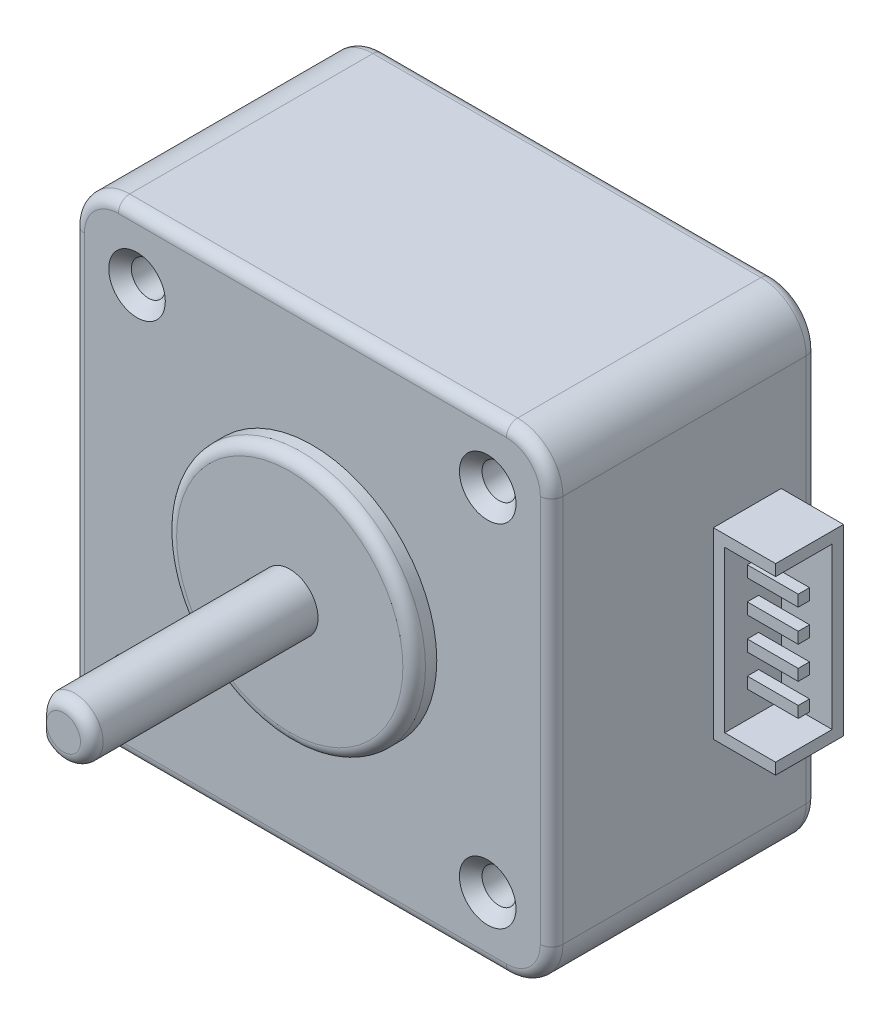
SolidWorks part; units mm, degrees
ref_plane "Top Plane" through (0, 0, 0) normal (0, 0, 1) x (1, 0, 0)
ref_plane "Right Plane" through (0, 0, 0) normal (0, 1, 0) x (1, 0, 0)
ref_plane "Front Plane" through (0, 0, 0) normal (1, 0, 0) x (0, 0, -1)
sketch "Sketch1" plane through (0, 0, 0) normal (0, 0, 1) x (1, 0, 0)
  line L0 (-21.15, 21.15) -> (21.15, -21.15) construction
  line L1 (-21.15, 21.15) -> (21.15, 21.15)
  line L2 (-21.15, 21.15) -> (-21.15, -21.15)
  line L3 (-21.15, -21.15) -> (21.15, -21.15)
  line L4 (21.15, 21.15) -> (21.15, -21.15)
  point P4 (0, 0)
  dimension "D1" = 42.3
extrude "Boss-Extrude1" add sketch "Sketch1" along normal blind 23.5
fillet "Fillet1" radius 4 4 edges at (-21.15, 21.15, 11.75) (21.15, 21.15, 11.75) (21.15, -21.15, 11.75) (-21.15, -21.15, 11.75)
sketch "Sketch2" plane through (0, 0, 23.5) normal (0, 0, 1) x (1, 0, 0)
  line L0 (-15.5, -15.5) -> (0, 0) construction
  line L1 (-15.5, -15.5) -> (-15.5, 0) construction
  line L2 (-15.5, 0) -> (0, 0) construction
  circle A0 centre (-15.5, -15.5) radius 1.5
  dimension "D1" = 3
  dimension "D2" = 15.5
extrude "Cut-Extrude1" cut sketch "Sketch2" against normal blind 5
chamfer "Chamfer1" distance 1 angle 45 1 edges at (-14, -15.5, 23.5)
ref_axis "Axis1" through (0, 0, 23.5) along (0, 0, 1)
pattern_circular "CirPattern1" count 4 over 360 about axis through (0, 0, 23.5) along (0, 0, 1) of "Cut-Extrude1", "Chamfer1"
sketch "Sketch3" plane through (0, 0, 23.5) normal (0, 0, 1) x (1, 0, 0)
  circle A0 centre (0, 0) radius 11
  dimension "D1" = 22
extrude "Boss-Extrude2" add sketch "Sketch3" along normal blind 2
sketch "Sketch4" plane through (0, 0, 25.5) normal (0, 0, 1) x (1, 0, 0)
  circle A0 centre (0, 0) radius 2.5
  dimension "D1" = 5
extrude "Boss-Extrude3" add sketch "Sketch4" along normal blind 20
fillet "Fillet2" radius 1 18 edges at (19.9784, -19.9784, 0) (0, -21.15, 0) (-19.9784, -19.9784, 0) (-21.15, 0, 0) (-19.9784, 19.9784, 0) (0, 21.15, 0) (19.9784, 19.9784, 0) (19.9784, 19.9784, 23.5) (21.15, 0, 23.5) (19.9784, -19.9784, 23.5) (0, -21.15, 23.5) (-19.9784, -19.9784, 23.5) (-21.15, 0, 23.5) (-19.9784, 19.9784, 23.5) (21.15, 0, 0) (0, 21.15, 23.5) (11, 0, 25.5) (2.5, 0, 45.5)
sketch "Sketch5" plane through (21.15, 0, 0) normal (1, 0, 0) x (0, 0, -1)
  line L0 (0, 17.15) -> (0, -17.15) construction
  line L1 (-9.2, -8.1) -> (-3.2, -8.1)
  line L2 (-9.2, -8.1) -> (-9.2, 8.1)
  line L3 (-9.2, 8.1) -> (-3.2, 8.1)
  line L4 (-3.2, -8.1) -> (-3.2, 8.1)
  line L5 (-3.2, 0) -> (0, 0) construction
  dimension "D1" = 9.2
  dimension "D2" = 16.2
  dimension "D3" = 6
extrude "Boss-Extrude4" add sketch "Sketch5" along normal blind 1
sketch "Sketch6" plane through (22.15, 0, 0) normal (1, 0, 0) x (0, 0, -1)
  line L0 (-9.2, -7.1) -> (-4.2, -7.1)
  line L1 (-4.2, -7.1) -> (-4.2, 7.1)
  line L2 (-4.2, 7.1) -> (-9.2, 7.1)
  line L3 (-9.2, -7.1) -> (-9.2, -8.1)
  line L4 (-9.2, 8.1) -> (-9.2, -8.1)
  line L5 (-9.2, -8.1) -> (-3.2, -8.1)
  line L6 (-3.2, -8.1) -> (-3.2, 8.1)
  line L7 (-3.2, 8.1) -> (-9.2, 8.1)
  line L8 (-9.2, 8.1) -> (-9.2, 7.1)
  line L9 (-9.2, -8.1) -> (-3.2, -8.1)
  line L10 (-3.2, -8.1) -> (-3.2, 8.1)
  line L11 (-3.2, 8.1) -> (-9.2, 8.1)
  line L12 (-9.2, 7.1) -> (-9.2, -7.1) construction
  line L13 (-4.2, -7.1) -> (-3.2, -7.1) construction
  line L14 (-6.7, -7.1) -> (-6.7, -4.26) construction
  line L15 (-7.2, -4.76) -> (-6.2, -4.76)
  line L16 (-3.2, 7.1) -> (-4.2, 7.1) construction
  line L17 (-7.2, -4.76) -> (-7.2, -3.76)
  line L18 (-7.2, -3.76) -> (-6.2, -3.76)
  line L19 (-6.2, -4.76) -> (-6.2, -3.76)
  line L20 (-6.7, -4.26) -> (-6.7, -1.42) construction
  line L21 (-6.7, 1.42) -> (-6.7, 4.26) construction
  line L22 (-6.7, 4.26) -> (-6.7, 7.1) construction
  line L23 (-6.2, -4.76) -> (-7.2, -3.76) construction
  line L28 (-7.2, 0.92) -> (-6.2, 0.92)
  line L29 (-7.2, 0.92) -> (-7.2, 1.92)
  line L30 (-7.2, 1.92) -> (-6.2, 1.92)
  line L31 (-6.2, 0.92) -> (-6.2, 1.92)
  line L32 (-6.2, 0.92) -> (-7.2, 1.92) construction
  line L33 (-7.2, 3.76) -> (-6.2, 3.76)
  line L34 (-7.2, 3.76) -> (-7.2, 4.76)
  line L35 (-7.2, 4.76) -> (-6.2, 4.76)
  line L36 (-6.2, 3.76) -> (-6.2, 4.76)
  line L37 (-6.2, 3.76) -> (-7.2, 4.76) construction
  line L38 (-7.2, -1.92) -> (-6.2, -1.92)
  line L39 (-7.2, -1.92) -> (-7.2, -0.92)
  line L40 (-7.2, -0.92) -> (-6.2, -0.92)
  line L41 (-6.2, -1.92) -> (-6.2, -0.92)
  line L42 (-6.2, -1.92) -> (-7.2, -0.92) construction
  line L43 (-6.7, -1.42) -> (-6.7, 1.42) construction
  point P16 (-6.7, -4.26)
  point P17 (-6.7, 1.42)
  point P18 (-6.7, 4.26)
  point P34 (-6.7, -1.42)
  point P35 (-6.7, -4.26)
  point P37 (-6.7, -1.42)
  point P38 (-6.7, 1.42)
  point P39 (-6.7, 4.26)
  dimension "D2" = 1
  dimension "D3" = 1
  dimension "D4" = 1
  dimension "D5" = 1
  dimension "D6" = 1
  dimension "D1" = 0
extrude "Boss-Extrude5" add sketch "Sketch6" along normal blind 4.5
sketch "Sketch7" plane through (0, 0, 45.5) normal (0, 0, 1) x (1, 0, 0)
  line L0 (-1.5, 0) -> (2.5, 0) construction
  line L1 (-1.5, -2) -> (-5.5, -2)
  line L2 (-1.5, -2) -> (-1.5, 2)
  line L3 (-1.5, 2) -> (-5.5, 2)
  line L4 (-5.5, -2) -> (-5.5, 2)
  circle A0 centre (0, 0) radius 2.5 construction
  point P8 (-1.658, 1.8711)
  point P9 (0, 0)
  dimension "D1" = 4
  dimension "D2" = 4
extrude "Cut-Extrude2" cut sketch "Sketch7" against normal blind 18
